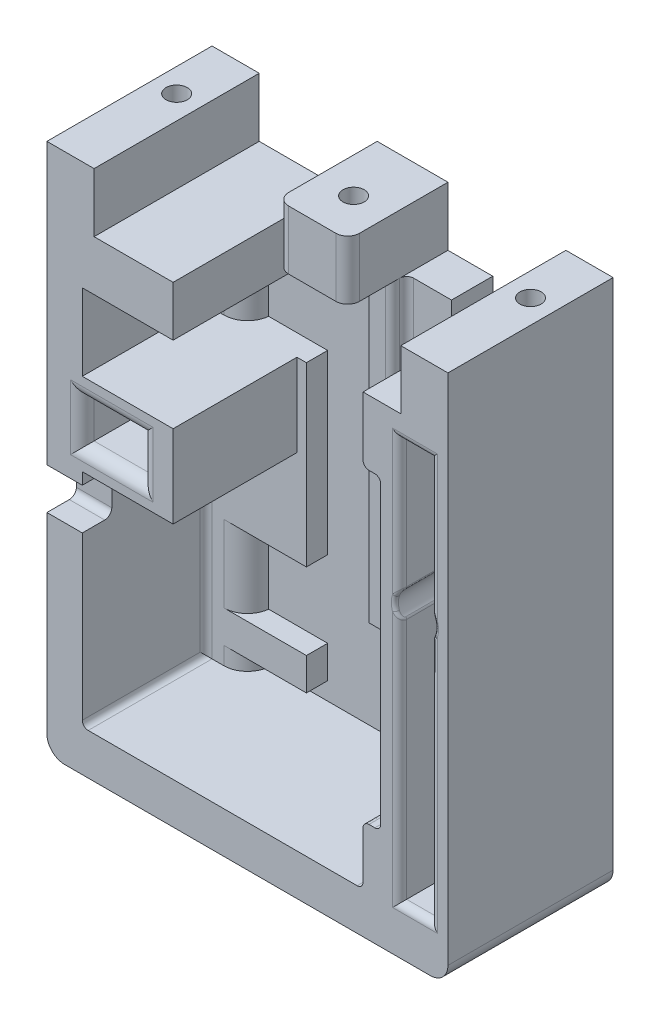
SolidWorks part; units mm, degrees
material "Nylon 101"
ref_plane "Ebene vorne" through (0, 0, 0) normal (0, 0, 1) x (1, 0, 0)
ref_plane "Ebene oben" through (0, 0, 0) normal (0, 1, 0) x (1, 0, 0)
ref_plane "Ebene rechts" through (0, 0, 0) normal (1, 0, 0) x (0, 0, -1)
sketch "front" plane through (0, 0, 0) normal (0, 0, 1) x (1, 0, 0)
  line L1 (-17, 22.5) -> (17, 22.5)
  line L2 (-17, 22.5) -> (-17, -22.5)
  line L3 (-17, -22.5) -> (17, -22.5)
  line L4 (17, 22.5) -> (17, -22.5)
  line L5 (-17, 22.5) -> (17, -22.5) construction
  line L6 (-17, -22.5) -> (17, 22.5) construction
  point P0 (0, 0)
  dimension "D1" = 34
  dimension "D2" = 45
extrude "front-body" add sketch "front" along normal mid plane 14
sketch "jig-channel" plane through (0, 0, 7) normal (0, 0, 1) x (1, 0, 0)
  line L0 (17, 22.5) -> (-17, 22.5) construction
  line L1 (8.3, 22.5) -> (9.8, 22.5)
  line L2 (8.3, 22.5) -> (8.3, -19)
  line L3 (8.3, -19) -> (9.8, -19)
  line L4 (9.8, 22.5) -> (9.8, -19)
  line L5 (17, -22.5) -> (17, 22.5) construction
  dimension "D1" = 41.5
  dimension "D2" = 1.5
  dimension "D3" = 7.2
extrude "jig-cut" cut sketch "jig-channel" against normal through all contours L2 L3 L4 L1
sketch "jig-channel-cut" plane through (0, 0, 7) normal (0, 0, 1) x (1, 0, 0)
  line L0 (8.3, 22.5) -> (8.3, -19) construction
  line L1 (8.3, 22.5) -> (6.8, 22.5)
  line L2 (8.3, 22.5) -> (8.3, -15.5)
  line L3 (8.3, -15.5) -> (6.8, -15.5)
  line L4 (6.8, 22.5) -> (6.8, -15.5)
  line L5 (-17, -22.5) -> (17, -22.5) construction
  dimension "D1" = 1.5
  dimension "D2" = 38
  dimension "D3" = 7
extrude "jig-channel cut" cut sketch "jig-channel-cut" against normal through all
sketch "rack-channle" plane through (0, 0, 7) normal (0, 0, 1) x (1, 0, 0)
  line L0 (6.8, 22.5) -> (-17, 22.5) construction
  line L1 (3, 22.5) -> (13, 22.5)
  line L2 (3, 22.5) -> (3, 17.5)
  line L3 (3, 17.5) -> (13, 17.5)
  line L4 (13, 22.5) -> (13, 17.5)
  line L5 (17, -22.5) -> (17, 22.5) construction
  line L6 (-17, 22.5) -> (-17, -22.5) construction
  line L7 (-13, 22.5) -> (-3, 22.5)
  line L8 (-13, 22.5) -> (-13, 17.5)
  line L9 (-13, 17.5) -> (-3, 17.5)
  line L10 (-3, 22.5) -> (-3, 17.5)
  dimension "D1" = 10
  dimension "D2" = 5
  dimension "D3" = 4
  dimension "D4" = 5
  dimension "D5" = 10
  dimension "D6" = 4
extrude "rack-channel" cut sketch "rack-channle" against normal through all
sketch "glider-range-cut" plane through (0, 0, 7) normal (0, 0, 1) x (1, 0, 0)
  line L0 (9.8, 17.5) -> (9.8, -19) construction
  line L1 (9.8, 12) -> (11.3, 12)
  line L2 (9.8, 12) -> (9.8, -14)
  line L3 (9.8, -14) -> (11.3, -14)
  line L4 (11.3, 12) -> (11.3, -14)
  line L5 (17, 22.5) -> (13, 22.5) construction
  point P6 (15, 22.5)
  dimension "D1" = 1.5
  dimension "D2" = 26
  dimension "D3" = 10.5
extrude "glider-rangecut" cut sketch "glider-range-cut" against normal through all
fillet "Verrundung2" radius 0.5 4 edges at (9.8, -14, 0) (11.3, -14, 0) (9.8, 12, 0) (11.3, 12, 0)
fillet "Verrundung3" radius 0.5 2 edges at (9.8, -19, 0) (8.3, -19, 0)
sketch "hollo-" plane through (0, 0, 7) normal (0, 0, 1) x (1, 0, 0)
  line L0 (-13, 22.5) -> (-17, 22.5) construction
  line L1 (-14, 17.5) -> (9, 17.5)
  line L2 (-14, 17.5) -> (-14, -19)
  line L3 (-14, -19) -> (9, -19)
  line L4 (9, 17.5) -> (9, -19)
  line L5 (-17, 22.5) -> (-17, -22.5) construction
  dimension "D1" = 36.5
  dimension "D2" = 23
  dimension "D3" = 5
  dimension "D4" = 3
extrude "hollo" cut sketch "hollo-" against normal blind 10.5
sketch "g-cut" plane through (0, 0, 7) normal (0, 0, 1) x (1, 0, 0)
  line L1 (-3, 22.5) -> (3, 22.5)
  line L2 (-3, 22.5) -> (-3, 17.5)
  line L3 (-3, 17.5) -> (3, 17.5)
  line L4 (3, 22.5) -> (3, 17.5)
extrude "gear-cut" cut sketch "g-cut" against normal blind 5.5
fillet "Verrundung5" radius 1 1 edges at (6.8, -15.5, -5.25)
fillet "Verrundung6" radius 1 1 edges at (8.3, -15.5, -5.25)
sketch "glider-location-" plane through (0, 0, -3.5) normal (0, 0, 1) x (1, 0, 0)
  line L0 (-3, 17.5) -> (-13, 17.5) construction
  line L1 (-5.5, 17.5) -> (1, 17.5)
  line L2 (-5.5, 17.5) -> (-5.5, -19)
  line L3 (-5.5, -19) -> (1, -19)
  line L4 (1, 17.5) -> (1, -19)
  line L5 (-14, -19) -> (8.8, -19) construction
  line L6 (-14, 17.5) -> (-14, -19) construction
  dimension "D1" = 6.5
  dimension "D2" = 8.5
extrude "glider-loc" cut sketch "glider-location-" against normal blind 1.8
fillet "Verrundung7" radius 0.5 1 edges at (-1, 17.5, -5.3)
sketch "glider-pin-out" plane through (0, 0, -3.5) normal (0, 0, 1) x (1, 0, 0)
  line L0 (-2.25, -19) -> (-2.25, 17.5) construction
  line L1 (-5.5, -19) -> (1, -19) construction
  line L2 (-3, 17.5) -> (3, 17.5) construction
  line L3 (-2.25, -0.75) -> (-5.5, -0.75) construction
  line L4 (-5.5, 17.5) -> (-5.5, -19) construction
  line L5 (-5.5, -0.75) -> (1, -0.75) construction
  line L6 (1, -19) -> (1, 17.5) construction
  line L7 (-14, 6.75) -> (6.8, 6.75) construction
  line L8 (-14, 17.5) -> (-14, -19) construction
  line L9 (6.8, -14.5) -> (6.8, 17.5) construction
  line L10 (6.8, -8.25) -> (-17, -8.25) construction
  line L11 (-17, 22.5) -> (-17, -22.5) construction
  line L12 (-5.5, 17.5) -> (-5.5, -19) construction
  line L13 (-5.5, 6.75) -> (-10.5, 6.75)
  line L14 (-5.5, 6.75) -> (-5.5, 13.25)
  line L15 (-5.5, 13.25) -> (-10.5, 13.25)
  line L16 (-10.5, 6.75) -> (-10.5, 13.25)
  line L19 (-5.5, 17.5) -> (-5.5, -19) construction
  line L20 (-5.5, -14.75) -> (-10.5, -14.75)
  line L21 (-5.5, -14.75) -> (-5.5, -8.25)
  line L22 (-5.5, -8.25) -> (-10.5, -8.25)
  line L23 (-10.5, -14.75) -> (-10.5, -8.25)
  line L24 (-10.5, -17.5) -> (-5.5, -17.5)
  line L25 (-10.5, -17.5) -> (-10.5, -19)
  line L26 (-10.5, -19) -> (-5.5, -19)
  line L27 (-5.5, -17.5) -> (-5.5, -19)
  line L28 (-14, -19) -> (-5.5, -19) construction
  dimension "D1" = 7.5
  dimension "D2" = 7.5
  dimension "D3" = 5
  dimension "D4" = 6.5
  dimension "D5" = 6.5
  dimension "D6" = 5
  dimension "D7" = 1.5
extrude "glider pins" cut sketch "glider-pin-out" against normal blind 1.8
sketch "motor-holder-block" plane through (0, 0, -3.5) normal (0, 0, 1) x (1, 0, 0)
  line L0 (-14, 17.5) -> (-14, -19) construction
  line L1 (-14, 6.75) -> (-6.3, 6.75)
  line L2 (-14, 6.75) -> (-14, -0.25)
  line L3 (-14, -0.25) -> (-6.3, -0.25)
  line L4 (-6.3, 6.75) -> (-6.3, -0.25)
  line L5 (-5.5, 13.25) -> (-10.5, 13.25) construction
  line L6 (-10.5, 6.75) -> (-5.5, 6.75) construction
  line L7 (-14, 17.5) -> (-6.3, 17.5)
  line L9 (-14, 17.5) -> (-14, 13.25)
  line L10 (-14, 13.25) -> (-6.3, 13.25)
  line L11 (-6.3, 17.5) -> (-6.3, 13.25)
  dimension "D1" = 7.7
  dimension "D2" = 7
  dimension "D3" = 0
  dimension "D4" = 7.7
extrude "motor-holder" add sketch "motor-holder-block" along normal blind 10.5
fillet "Verrundung9" radius 1 2 edges at (3, 20, 1.5) (-3, 20, 1.5)
sketch "bore" plane through (0, 22.5, 0) normal (0, 1, 0) x (1, 0, 0)
  line L0 (-13, 7) -> (-17, 7) construction
  line L3 (-13, 7) -> (-13, -7) construction
  line L4 (17, -7) -> (17, 7) construction
  line L5 (17, 7) -> (13, 7) construction
  circle A0 centre (-15, 2) radius 0.9
  circle A1 centre (15, 2) radius 0.9
  dimension "D1" = 1.8
  dimension "D4" = 2
  dimension "D2" = 5
  dimension "D3" = 2
  dimension "D5" = 5
extrude "screw-bore" cut sketch "bore" against normal blind 10
sketch "bore2" plane through (0, 22.5, 0) normal (0, 1, 0) x (1, 0, 0)
  line L0 (3, 7) -> (-3, 7) construction
  line L1 (-3, 7) -> (-3, -0.5) construction
  circle A0 centre (0, 2) radius 0.9
  point P2 (0, 7)
  dimension "D1" = 5
  dimension "D3" = 1.8
  dimension "D2" = 3
extrude "top-middle-screw-bore" cut sketch "bore2" against normal blind 5
sketch "fit" plane through (0, 0, 7) normal (0, 0, 1) x (1, 0, 0)
  line L1 (-14, 5) -> (-9, 5)
  line L2 (-14, 5) -> (-14, 1.5)
  line L3 (-14, 1.5) -> (-9, 1.5)
  line L4 (-9, 5) -> (-9, 1.5)
  line L5 (-17, -22.5) -> (17, -22.5) construction
  line L6 (-17, 22.5) -> (-17, -22.5) construction
  dimension "D1" = 3.5
  dimension "D2" = 24
  dimension "D3" = 5
  dimension "D4" = 3
extrude "fit-cut" cut sketch "fit" against normal blind 12
fillet "Verrundung10" radius 1 4 edges at (-9, 3.25, 7) (-11.5, 1.5, 7) (-14, 3.25, -5) (-11.5, 5, 7)
fillet "Verrundung11" radius 1 1 edges at (-14, 3.25, 7)
sketch "fitcut2" plane through (0, 0, 7) normal (0, 0, 1) x (1, 0, 0)
  line L0 (17, -22.5) -> (17, 22.5) construction
  line L1 (12.9, 15.5) -> (15.5, 15.5)
  line L2 (12.9, 15.5) -> (12.9, -18.5)
  line L3 (12.9, -18.5) -> (15.5, -18.5)
  line L4 (15.5, 15.5) -> (15.5, -18.5)
  line L6 (-17, -22.5) -> (17, -22.5) construction
  dimension "D1" = 2.6
  dimension "D2" = 1.5
  dimension "D3" = 34
  dimension "D4" = 4
extrude "fit-cut2" cut sketch "fitcut2" against normal blind 10
fillet "Verrundung12" radius 0.6 4 edges at (14.2, -18.5, 7) (14.2, 15.5, 7) (12.9, -1.5, 7) (15.5, -1.5, 7)
sketch "glider more-holder" plane through (0, 0, -5.3) normal (0, 0, 1) x (1, 0, 0)
  line L0 (1, -19) -> (1, 17.5) construction
  line L1 (1, 17.5) -> (3, 17.5)
  line L2 (1, 17.5) -> (1, -8.5)
  line L3 (1, -8.5) -> (3, -8.5)
  line L4 (3, 17.5) -> (3, -8.5)
  line L5 (6.8, 17.5) -> (3, 17.5) construction
  dimension "D1" = 2
  dimension "D2" = 0
  dimension "D3" = 26
extrude "glider-more" add sketch "glider more-holder" along normal blind 3
fillet "Verrundung13" radius 0.6 1 edges at (3, 4.5, -3.5)
fillet "Verrundung14" radius 0.6 1 edges at (3, 4.5, -2.3)
sketch "cable-out" plane through (0, 0, 7) normal (0, 0, 1) x (1, 0, 0)
  line L0 (-17, 22.5) -> (-17, -22.5) construction
  line L1 (-17, -4.75) -> (-14, -4.75)
  line L2 (-17, -4.75) -> (-17, -1.25)
  line L3 (-17, -1.25) -> (-14, -1.25)
  line L4 (-14, -4.75) -> (-14, -1.25)
  line L5 (-14, -0.25) -> (-14, -19) construction
  line L6 (-14, -0.25) -> (-6.3, -0.25) construction
  dimension "D1" = 3.5
  dimension "D2" = 1
extrude "cable-out-channel" cut sketch "cable-out" against normal blind 2.5
fillet "Verrundung15" radius 0.6 2 edges at (-15.5, -1.25, 4.5) (-15.5, -4.75, 4.5)
fillet "Verrundung16" radius 1.5 2 edges at (-17, -22.5, 0) (17, -22.5, 0)
fillet "Verrundung23" radius 0.5 3 edges at (-14, 10, -3.5) (-14, -9.625, -3.5) (-14, -19, 1.75)
fillet "Verrundung24" radius 2 2 edges at (-10.5, 10, -3.5) (-10.5, -11.5, -3.5)
fillet "Verrundung25" radius 2 1 edges at (-10.5, -18.25, -3.5)
fillet "Verrundung26" radius 2 1 edges at (-5.5, 15.375, -3.5)
sketch "screw" plane through (0, 0, -5) normal (0, 0, 1) x (1, 0, 0)
  line L0 (-11, 5) -> (-11, 1.7977) construction
  line L1 (-9, 5) -> (-13, 5) construction
  line L2 (-13, 3.25) -> (-9, 3.25) construction
  line L3 (-13, 5) -> (-13, 1.5) construction
  line L4 (-9, 1.5) -> (-9, 5) construction
  line L5 (14.2, 15.5) -> (14.2, -18.5) construction
  line L6 (15.5, 15.5) -> (12.9, 15.5) construction
  circle A0 centre (-11, 3.25) radius 1.7
  circle A1 centre (14.2, 3.25) radius 1.7
  dimension "D1" = 3.4
  dimension "D2" = 3.4
extrude "screw-hole" cut sketch "screw" against normal through all both and the other way through all
fillet "Verrundung27" radius 0.3 6 edges at (12.9, 4.3454, 1.7) (12.9, 2.1546, 1.7) (15.5, 2.1546, 1.7) (15.5, 4.3454, 1.7) (12.5067, 3.0988, 6.9633) (15.8933, 3.4012, 6.9633)
